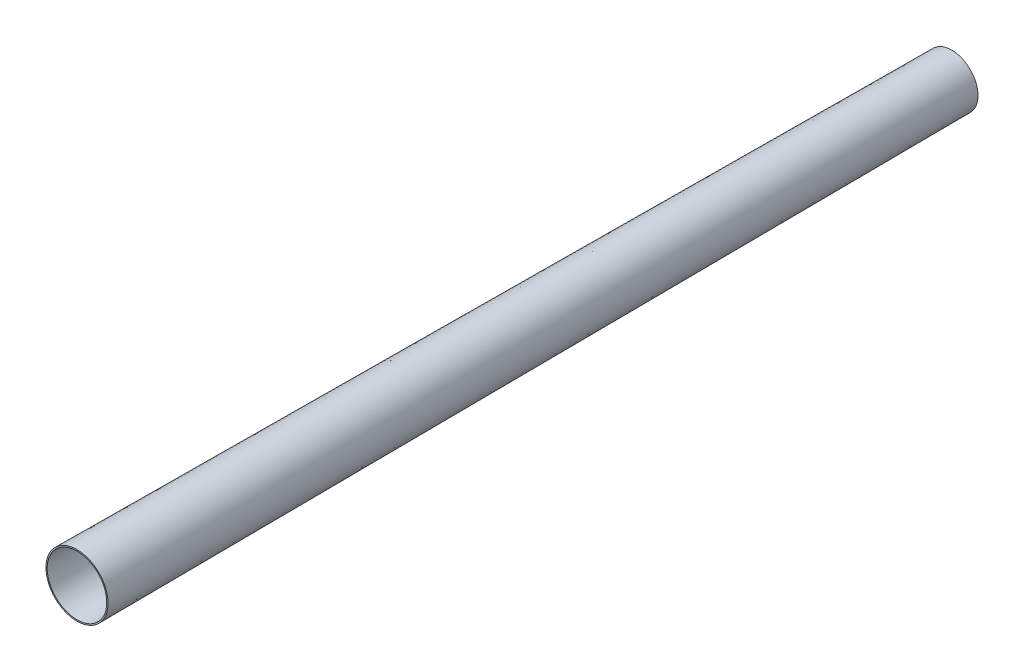
SolidWorks part; units mm, degrees
ref_plane "Front Plane" through (0, 0, 0) normal (0, 0, 1) x (1, 0, 0)
ref_plane "Top Plane" through (0, 0, 0) normal (0, 1, 0) x (1, 0, 0)
ref_plane "Right Plane" through (0, 0, 0) normal (1, 0, 0) x (0, 0, -1)
sketch "Sketch1" plane through (0, 0, 0) normal (0, 0, 1) x (1, 0, 0)
  circle A0 centre (0, 0) radius 9.992
  circle A1 centre (0, 0) radius 10.492
  dimension "D2" = 20.9841
  dimension "D1" = 0.5
ref_plane "Plane1" through (0, 0, 349.7002) normal (0, 0, 1) x (1, 0, 0)
sketch "Sketch2" plane through (0, 0, 349.7002) normal (0, 0, 1) x (1, 0, 0)
  circle A0 centre (0, 0) radius 12.4044
  circle A1 centre (0, 0) radius 11.9044
  dimension "D2" = 24.8088
  dimension "D1" = 0.5
loft "Loft1" add section "Sketch1" section "Sketch2" start constraint default connector at (-9.4907, -4.4733, 0) connector at (-11.2371, -5.2533, 349.7002)
shell "Shell1" thickness 0.5 removed face at (10.492, 0, 0) removed face at (12.4044, 0, 349.7002)
